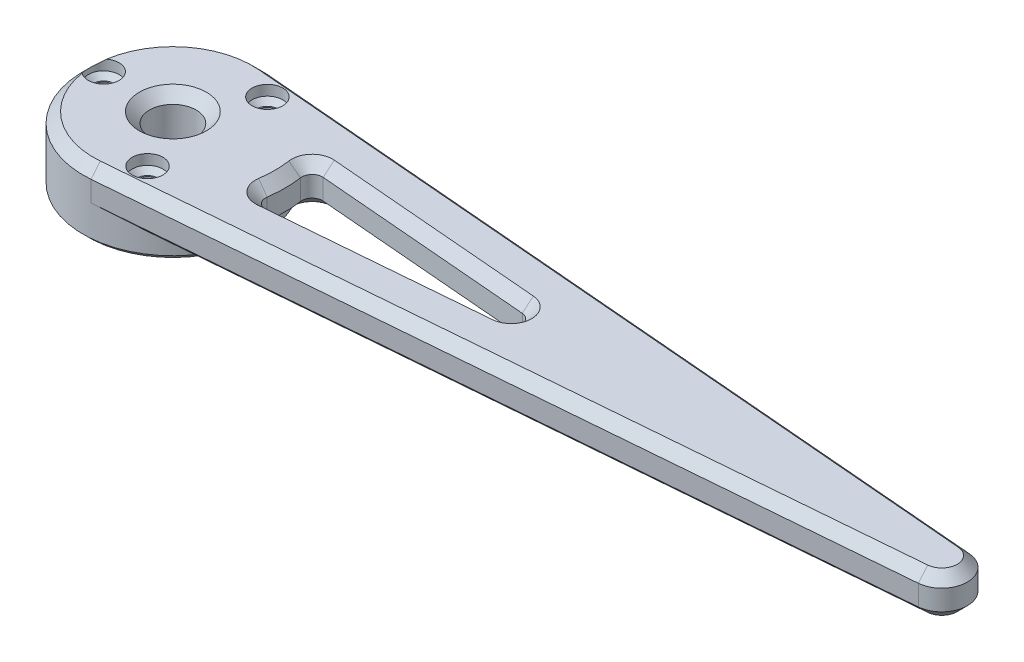
SolidWorks part; units mm, degrees
ref_plane "Front Plane" through (0, 0, 0) normal (0, 0, 1) x (1, 0, 0)
ref_plane "Top Plane" through (0, 0, 0) normal (0, 1, 0) x (1, 0, 0)
ref_plane "Right Plane" through (0, 0, 0) normal (1, 0, 0) x (0, 0, -1)
sketch "Sketch1" plane through (0, 0, 0) normal (0, 1, 0) x (1, 0, 0)
  line L0 (1.4583, 17.4391) -> (150.4167, 4.9826)
  line L1 (-45.5871, 0) -> (110.9335, 0) construction
  line L2 (1.4583, -17.4391) -> (150.4167, -4.9826)
  line L3 (6.75, 11.6913) -> (-13.5, 0) construction
  line L4 (-13.5, 0) -> (6.75, -11.6913) construction
  line L5 (6.75, -11.6913) -> (6.75, 11.6913) construction
  arc A0 (1.4583, 17.4391) -> (1.4583, -17.4391) centre (0, 0) ccw
  arc A1 (150.4167, -4.9826) -> (150.4167, 4.9826) centre (150, 0) ccw
  circle A2 centre (0, 0) radius 13.5 construction
  circle A3 centre (6.75, 11.6913) radius 1.75
  circle A4 centre (-13.5, 0) radius 1.75
  circle A5 centre (6.75, -11.6913) radius 1.75
  dimension "D1" = 27
  dimension "D2" = 3.5
  dimension "D4" = 17.5
  dimension "D5" = 5
  dimension "D3" = 150
extrude "Boss-Extrude1" add sketch "Sketch1" along normal blind 8
sketch "Sketch2" plane through (0, 8, 0) normal (0, 1, 0) x (1, 0, 0)
  circle A0 centre (6.75, -11.6913) radius 3
  circle A1 centre (6.75, 11.6913) radius 3
  circle A2 centre (-13.5, 0) radius 3
  dimension "D1" = 6
extrude "Cut-Extrude1" cut sketch "Sketch2" against normal blind 3
sketch "Sketch3" plane through (0, 8, 0) normal (0, 1, 0) x (1, 0, 0)
  line L4 (0.625, -7.4739) -> (90, 0)
  line L5 (90, 0) -> (0.625, 7.4739)
  line L6 (21.1215, -5.7599) -> (90, 0)
  line L7 (90, 0) -> (21.1215, 5.7599)
  arc A2 (21.1215, -5.7599) -> (21.1215, 5.7599) centre (0, 0) ccw
  arc A4 (0.625, 7.4739) -> (0.625, -7.4739) centre (0, 0) ccw
  dimension "D1" = 10
extrude "Cut-Extrude2" cut sketch "Sketch3" against normal through all
fillet "Fillet1" radius 2 3 edges at (90, 4, 0) (21.1215, 4, 5.7599) (21.1215, 4, -5.7599)
chamfer "Chamfer1" distance 1 angle 45 3 edges at (6.75, 5, 14.6913) (-13.5, 5, 3) (6.75, 5, -8.6913)
sketch "Sketch4" plane through (0, 8, 0) normal (0, 1, 0) x (1, 0, 0)
  circle A0 centre (0, 0) radius 4.5416
extrude "Cut-Extrude3" cut sketch "Sketch4" against normal through all
sketch "Sketch5" plane through (0, 0, 0) normal (0, -1, 0) x (1, 0, 0)
  circle A0 centre (0, 0) radius 17.5
  circle A1 centre (0, 0) radius 4.5416
  circle A2 centre (6.75, 11.6913) radius 1.75
  circle A3 centre (6.75, -11.6913) radius 1.75
  circle A4 centre (-13.5, 0) radius 1.75
  circle A5 centre (6.75, -11.6913) radius 1.75 construction
  circle A6 centre (0, 0) radius 4.5416 construction
  arc A7 (1.4583, 17.4391) -> (1.4583, -17.4391) centre (0, 0) ccw construction
extrude "Boss-Extrude2" add sketch "Sketch5" along normal blind 5
chamfer "Chamfer2" distance 2 angle 45 20 edges at (68, 0, 0) (44.981, 0, -3.7647) (44.981, 0, 3.7647) (22.1689, 0, -4.9105) (22.1689, 0, 4.9105) (21.8928, 0, 0) (22.1689, 8, -4.9105) (21.8928, 8, 0) (44.981, 8, -3.7647) (22.1689, 8, 4.9105) (68, 8, 0) (44.981, 8, 3.7647) (75.9375, 0, -11.2109) (155, 0, 0) (75.9375, 0, 11.2109) (155, 8, 0) (0, 8, 4.5416) (75.9375, 8, -11.2109) (75.9375, 8, 11.2109) (-17.5, 8, 0)
chamfer "Chamfer3" distance 1 angle 45 1 edges at (0, -5, -17.5)
